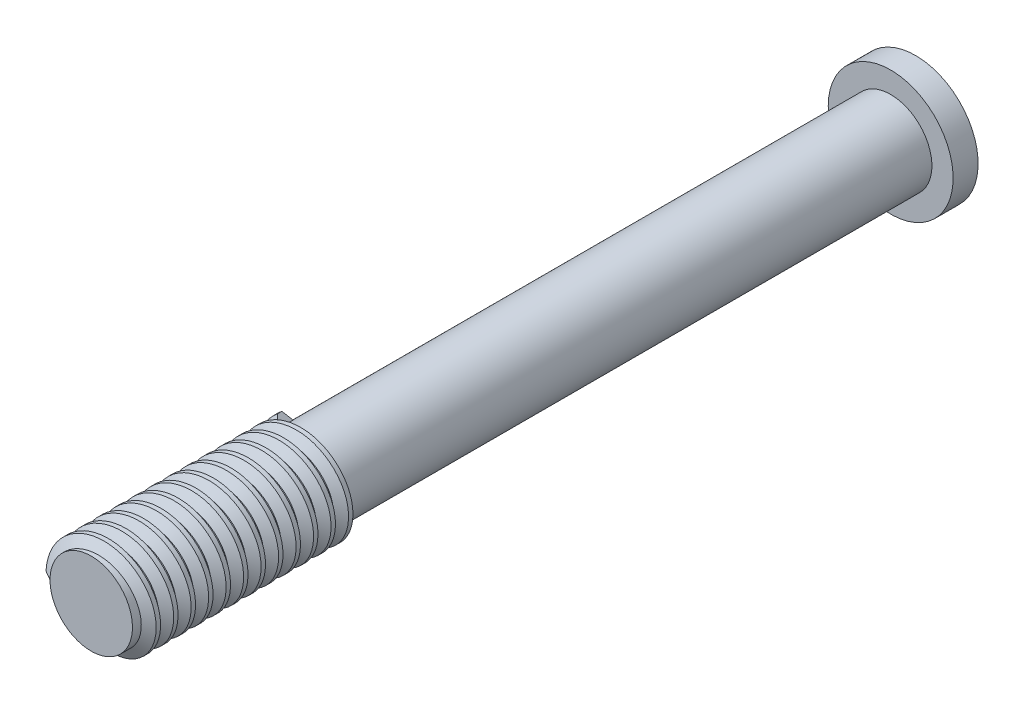
SolidWorks part; units mm, degrees
ref_plane "Front Plane" through (0, 0, 0) normal (0, 0, 1) x (1, 0, 0)
ref_plane "Top Plane" through (0, 0, 0) normal (0, 1, 0) x (1, 0, 0)
ref_plane "Right Plane" through (0, 0, 0) normal (1, 0, 0) x (0, 0, -1)
sketch "Sketch2" plane through (0, 0, 0) normal (0, 0, 1) x (1, 0, 0)
  circle A0 centre (0, 0) radius 1.65
  dimension "D1" = 3.3
extrude "Boss-Extrude1" add sketch "Sketch2" along normal blind 32
sketch "Sketch4" plane through (0, 0, 0) normal (0, 0, -1) x (-1, 0, 0)
  circle A0 centre (0, 0) radius 2.5
  dimension "D1" = 5
extrude "Boss-Extrude2" add sketch "Sketch4" along normal blind 1
thread "Thread1" pitch 0.7 method extrude profile "Thread Profile1" start angle 0, offset 0, length 8.5, pitch 0.7, diameter 3.3
ref_plane "Plane1" through (-1.65, 0, 32) normal (0, -1, 0) x (-1, 0, 0)
sketch "Thread Profile1" plane through (-1.65, 0, 32) normal (0, -1, 0) x (-1, 0, 0)
  line L0 (0, 0) -> (0, 0.7) construction
  line L11 (0, 0.6125) -> (0, 0)
  line L12 (0, 0) -> (0.3789, 0.2188)
  line L13 (0.3789, 0.2188) -> (0.3789, 0.3938)
  line L15 (0.3789, 0.3938) -> (0, 0.6125)
  line L17 (0.3789, 0.3063) -> (0, 0.3063) construction
  point P3 (0, 0)
  dimension "Pitch" = 0.7
  dimension "Profile_Angle" = 60
  dimension "Profile_Land" = 0.175
  dimension "Profile_Height" = 0.3789
